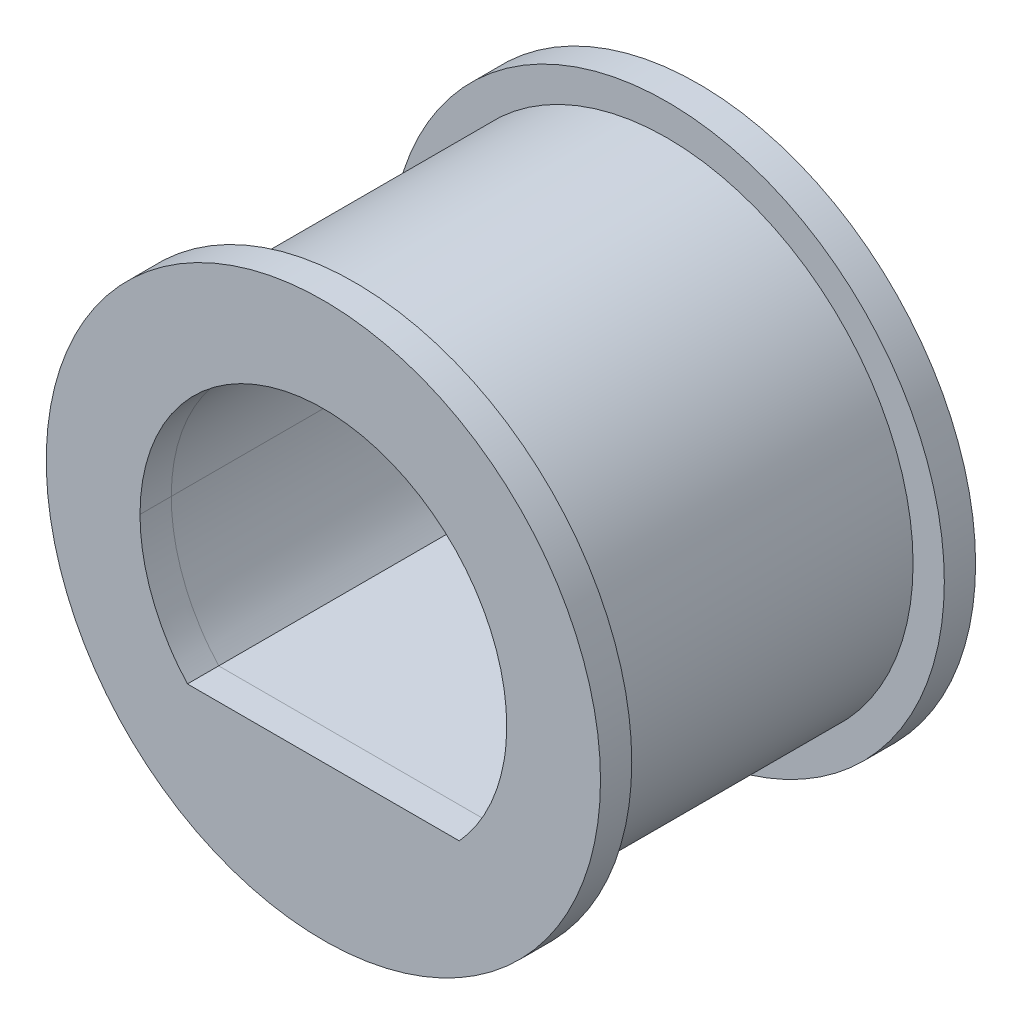
SolidWorks part; units mm, degrees
material "ABS"
ref_plane "Front Plane" through (0, 0, 0) normal (0, 0, 1) x (1, 0, 0)
ref_plane "Top Plane" through (0, 0, 0) normal (0, 1, 0) x (1, 0, 0)
ref_plane "Right Plane" through (0, 0, 0) normal (1, 0, 0) x (0, 0, -1)
sketch "Sketch1" plane through (0, 0, 0) normal (0, 0, 1) x (1, 0, 0)
  line L3 (-13.4806, 5.3614) -> (-15.6898, 5.3614)
  arc A6 (-13.0952, 6.3614) -> (-16.0752, 6.3614) centre (-14.5852, 6.3614) ccw
  circle A7 centre (-14.5852, 6.3614) radius 1.998
  circle A8 centre (-14.5852, 6.3614) radius 2.252
  spline S6 degree 3 poles (-16.0752, 6.3614) (-16.0746, 6.3309) (-16.0736, 6.27) (-16.0649, 6.179) (-16.0487, 6.0737) (-16.0209, 5.9549) (-15.9774, 5.8248) (-15.9223, 5.6991) (-15.8557, 5.5793) (-15.779, 5.4654) (-15.7195, 5.3961) (-15.6898, 5.3614) knots 0 0 0 0 0.083398 0.166639 0.250037 0.375031 0.500025 0.625018 0.750012 0.875006 1 1 1 1
  spline S7 degree 3 poles (-13.4806, 5.3614) (-13.4605, 5.3843) (-13.4205, 5.4302) (-13.3658, 5.5035) (-13.3072, 5.5925) (-13.248, 5.6992) (-13.1929, 5.8248) (-13.1494, 5.9549) (-13.1184, 6.0885) (-13.0988, 6.2244) (-13.0964, 6.3157) (-13.0952, 6.3614) knots 0 0 0 0 0.083398 0.166639 0.250037 0.375031 0.500025 0.625018 0.750012 0.875006 1 1 1 1
  dimension "D3" = 0.508
  dimension "D4" = 0.254
extrude "Boss-Extrude1" add sketch "Sketch1" along normal mid plane 2.54 contours A7 S7 L3 S6 A6 region at (-16.5267, 6.3614, 0)
extrude "Boss-Extrude2" add sketch "Sketch1<5>" along normal blind 0.254 from surface separate body contours A8 A7 | A7 S7 L3 S6 A6 region at (-16.5267, 6.3614, 0) region at (-16.7735, 6.3614, 0) starting at face at (-14.0329, 5.8614, 1.27)
sketch "Sketch1<5>" plane through (0, 0, 0) normal (0, 0, 1) x (1, 0, 0) same geometry as "Sketch1"
mirror "Mirror2" about plane through (0, 0, 0) normal (0, 0, 1) of bodies 102
